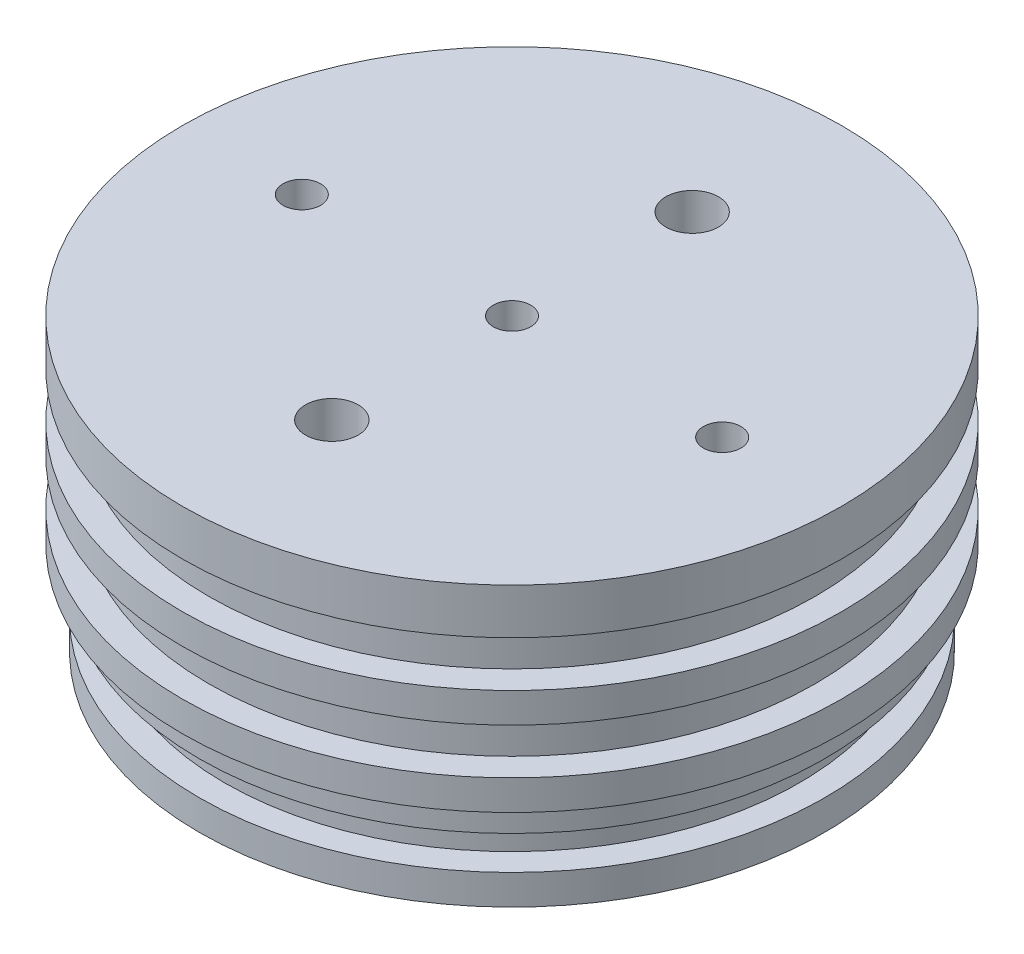
SolidWorks part; units mm, degrees
ref_plane "Front Plane" through (0, 0, 0) normal (0, 0, 1) x (1, 0, 0)
ref_plane "Top Plane" through (0, 0, 0) normal (0, 1, 0) x (1, 0, 0)
ref_plane "Right Plane" through (0, 0, 0) normal (1, 0, 0) x (0, 0, -1)
sketch "Sketch1" plane through (0, 0, 0) normal (0, 1, 0) x (1, 0, 0)
  circle A0 centre (0, 0) radius 69.723
  dimension "D1" = 139.446
extrude "Boss-Extrude1" add sketch "Sketch1" along normal blind 41.656
ref_plane "Plane1" through (69.723, 0, 0) normal (1, 0, 0) x (0, 0, -1)
sketch "Sketch3" plane through (0, 0, 0) normal (1, 0, 0) x (0, 0, -1)
  line L0 (69.723, 0) -> (69.723, 41.656) construction
  line L1 (69.723, 32.004) -> (64.135, 32.004)
  line L2 (69.723, 32.004) -> (69.723, 22.352)
  line L3 (69.723, 22.352) -> (64.135, 22.352)
  line L4 (64.135, 32.004) -> (64.135, 22.352)
  line L5 (-69.723, 0) -> (69.723, 0) construction
  line L6 (69.723, 16.002) -> (64.135, 16.002)
  line L7 (69.723, 16.002) -> (69.723, 6.35)
  line L8 (69.723, 6.35) -> (64.135, 6.35)
  line L9 (64.135, 16.002) -> (64.135, 6.35)
  dimension "D1" = 9.652
  dimension "D2" = 9.652
  dimension "D3" = 64.135
  dimension "D4" = 64.135
  dimension "D5" = 6.35
  dimension "D6" = 6.35
ref_axis "Axis1" through (0, 41.656, 0) along (0, -1, 0)
revolve "Cut-Revolve1" cut sketch "Sketch3" angle 360 about axis through (0, 41.656, 0) along (0, -1, 0)
sketch "Sketch4" plane through (0, 0, 0) normal (0, -1, 0) x (1, 0, 0)
  circle A0 centre (0, 0) radius 66.167
  dimension "D1" = 132.334
extrude "Boss-Extrude2" add sketch "Sketch4" along normal blind 19.8374
sketch "Sketch5" plane through (0, 0, 0) normal (1, 0, 0) x (0, 0, -1)
  line L0 (66.167, -19.8374) -> (66.167, 0) construction
  line L1 (66.167, -13.4874) -> (60.7695, -13.4874)
  line L2 (66.167, -13.4874) -> (66.167, -6.35)
  line L3 (66.167, -6.35) -> (60.7695, -6.35)
  line L4 (60.7695, -13.4874) -> (60.7695, -6.35)
  line L6 (-66.167, -19.8374) -> (66.167, -19.8374) construction
  dimension "D1" = 60.7695
  dimension "D2" = 7.1374
  dimension "D3" = 6.35
revolve "Cut-Revolve2" cut sketch "Sketch5" angle 360 about axis through (0, 41.656, 0) along (0, -1, 0)
sketch "Sketch7" plane through (0, -19.8374, 0) normal (0, -1, 0) x (1, 0, 0)
  circle A0 centre (0, 0) radius 24.765
  dimension "D1" = 49.53
extrude "Cut-Extrude1" [suppressed] cut sketch "Sketch7" against normal blind 38.1 contours A0
sketch "Sketch8" plane through (0, 41.656, 0) normal (0, 1, 0) x (1, 0, 0)
  line L0 (0, 0) -> (0, 38.1) construction
  line L1 (0, -33.8214) -> (0, 33.8214) construction
  dimension "D1" = 38.1
hole_wizard "Pipe Tap Drill for 1/4 Tap1" positions "3DSketch1" profile "Sketch9" hole size "1/4" standard "ANSI Inch" end condition up to next
sketch3d "3DSketch1"
  point P0 (0, 41.656, -38.1)
sketch "Sketch9" plane through (0, 41.656, -38.1) normal (1, 0, 0) x (0, 0, 1)
  line L0 (0, 0) -> (0, 61.4934)
  line L1 (0, 61.4934) -> (5.5626, 61.4934)
  line L2 (5.5626, 61.4934) -> (5.5626, 0)
  line L5 (5.5626, 0) -> (0, 0)
  line L11 (0, -6.35) -> (0, 107.95) construction
  dimension "Thru Hole Dia." = 11.1252
  dimension "Thru Hole Depth" = 61.4934
mirror "Mirror1" about plane through (0, 0, 0) normal (0, 0, 1) of "Pipe Tap Drill for 1/4 Tap1"
sketch "Sketch13" plane through (0, 41.656, 0) normal (0, 1, 0) x (1, 0, 0)
  point P0 (0, 0)
hole_wizard "Tap Drill for 3/8-16 Tap1" positions "3DSketch4" profile "Sketch16" hole size "3/8-16" standard "ANSI Inch"
sketch3d "3DSketch4"
  point P0 (0, 41.656, 0)
sketch "Sketch16" plane through (0, 41.656, 0) normal (1, 0, 0) x (0, 0, 1)
  line L0 (0, 0) -> (0, 27.7847)
  line L1 (0, 27.7847) -> (3.9687, 25.4)
  line L2 (3.9687, 25.4) -> (3.9687, 0)
  line L5 (3.9687, 0) -> (0, 0)
  line L10 (0, 27.7847) -> (-3.9688, 25.4) construction
  line L11 (0, -6.35) -> (0, 107.95) construction
  dimension "Hole Dia." = 7.9375
  dimension "Hole Depth" = 25.4
  dimension "Drill Angle" = 118
sketch "Sketch21" plane through (0, 41.656, 0) normal (0, 1, 0) x (1, 0, 0)
  point P0 (0, 38.1)
  point P1 (0, -38.1)
hole_wizard "Pipe Tap Drill for 1/4 Tap2" positions "3DSketch9" profile "Sketch23" hole size "1/4" standard "ANSI Inch" end condition up to next
sketch3d "3DSketch9"
  point P0 (0, 41.656, 38.1)
  point P3 (0, 41.656, -38.1)
sketch "Sketch23" plane through (0, 41.656, 38.1) normal (1, 0, 0) x (0, 0, 1)
  line L0 (0, 0) -> (0, 61.4934)
  line L1 (0, 61.4934) -> (5.5626, 61.4934)
  line L2 (5.5626, 61.4934) -> (5.5626, 0)
  line L5 (5.5626, 0) -> (0, 0)
  line L11 (0, -6.35) -> (0, 107.95) construction
  dimension "Thru Hole Dia." = 11.1252
  dimension "Thru Hole Depth" = 61.4934
sketch "snap ring groove" [suppressed] plane through (0, 0, 0) normal (0, 0, 1) x (1, 0, 0)
  line L2 (-66.167, -19.8374) -> (66.167, -19.8374) construction
  line L3 (-24.765, -16.6624) -> (-26.9494, -16.6624)
  line L4 (-24.765, -16.6624) -> (-24.765, -14.8844)
  line L5 (-24.765, -14.8844) -> (-26.9494, -14.8844)
  line L6 (-26.9494, -16.6624) -> (-26.9494, -14.8844)
  line L7 (-24.765, 18.2626) -> (-24.765, -19.8374) construction
  point P9 (-26.9494, -15.7734)
  dimension "D1" = 1.778
  dimension "D2" = 26.9494
  dimension "D3" = 3.175
revolve "Cut-Revolve3" [suppressed] cut sketch "snap ring groove" angle 360 about axis through (0, 41.656, 0) along (0, -1, 0)
sketch "Sketch24" plane through (0, 41.656, 0) normal (0, 1, 0) x (1, 0, 0)
  line L0 (-33.8214, 0) -> (33.8214, 0) construction
  point P0 (-44.45, 0)
  point P1 (44.45, 0)
  point P4 (0, 0)
  dimension "D1" = 44.45
  dimension "D2" = 44.45
hole_wizard "Tap Drill for 3/8-16 Tap2" positions "3DSketch11" profile "Sketch26" hole size "3/8-16" standard "ANSI Inch"
sketch3d "3DSketch11"
  point P0 (-44.45, 41.656, 0)
  point P3 (44.45, 41.656, 0)
sketch "Sketch26" plane through (-44.45, 41.656, 0) normal (1, 0, 0) x (0, 0, 1)
  line L0 (0, 0) -> (0, 21.4347)
  line L1 (0, 21.4347) -> (3.9687, 19.05)
  line L2 (3.9687, 19.05) -> (3.9687, 0)
  line L5 (3.9687, 0) -> (0, 0)
  line L10 (0, 21.4347) -> (-3.9688, 19.05) construction
  line L11 (0, -6.35) -> (0, 107.95) construction
  dimension "Hole Dia." = 7.9375
  dimension "Hole Depth" = 19.05
  dimension "Drill Angle" = 118
